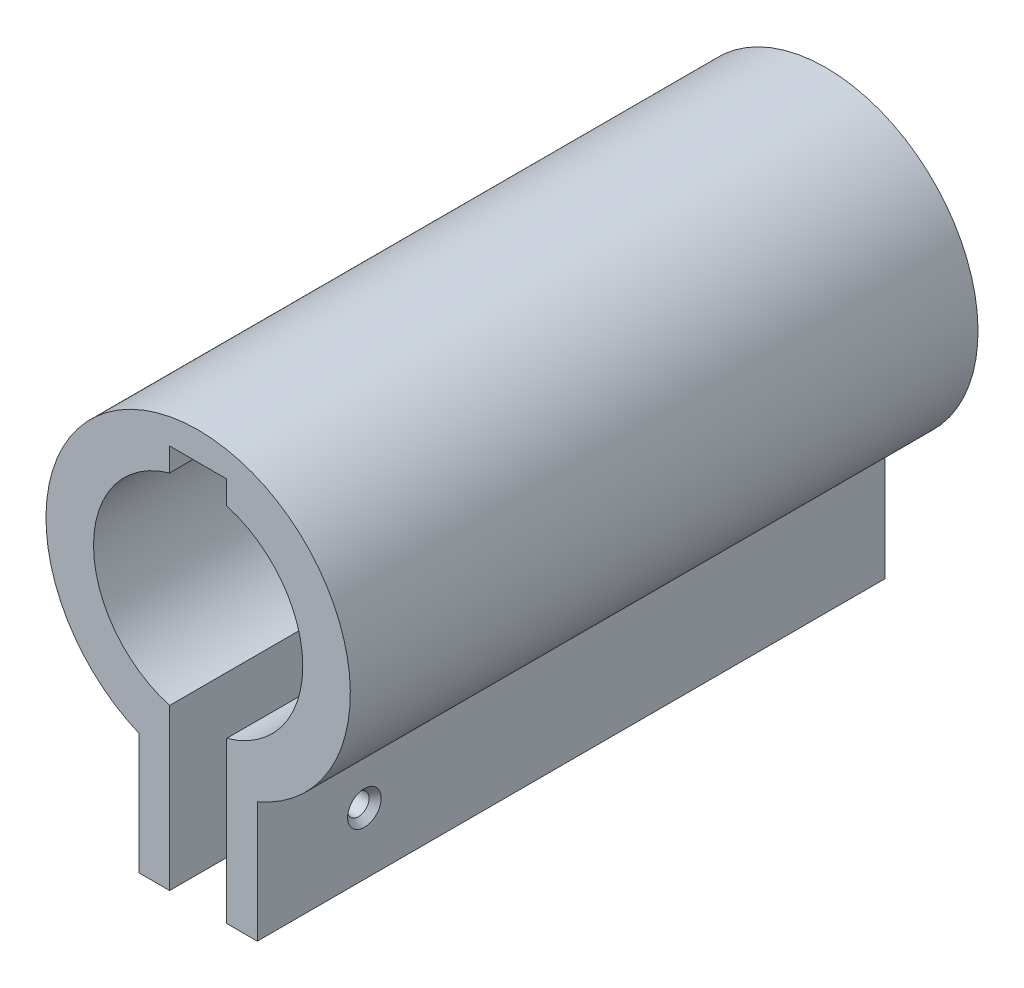
SolidWorks part; units mm, degrees
ref_plane "Front Plane" through (0, 0, 0) normal (0, 0, 1) x (1, 0, 0)
ref_plane "Top Plane" through (0, 0, 0) normal (0, 1, 0) x (1, 0, 0)
ref_plane "Right Plane" through (0, 0, 0) normal (1, 0, 0) x (0, 0, -1)
sketch "Sketch1" plane through (0, 0, 0) normal (0, 0, 1) x (1, 0, 0)
  circle A0 centre (0, 0) radius 11
  circle A1 centre (0, 0) radius 16
  dimension "D1" = 22
  dimension "D2" = 5
extrude "Boss-Extrude1" add sketch "Sketch1" along normal blind 33 and the other way blind 33
sketch "Sketch2" plane through (0, 0, 33) normal (0, 0, 1) x (1, 0, 0)
  line L0 (-3, 10.5402) -> (-3, 13.0402)
  line L2 (3, 13.0402) -> (3, 10.5402)
  line L3 (0, 0) -> (0, 13.0402) construction
  line L4 (-3, 13.0402) -> (0, 13.0402)
  line L5 (0, 13.0402) -> (3, 13.0402)
  line L6 (0, 0) -> (-3, 10.5402) construction
  line L7 (0, 0) -> (3, 10.5402) construction
  arc A0 (-3, 10.5402) -> (3, 10.5402) centre (0, 0) cw
  dimension "D1" = 3
  dimension "D2" = 3
  dimension "D3" = 2.5
extrude "Cut-Extrude1" cut sketch "Sketch2" against normal blind 33
mirror "Mirror2" about plane through (0, 0, 0) normal (0, 0, -1) of "Cut-Extrude1"
sketch "Sketch3" plane through (0, 0, 33) normal (0, 0, 1) x (1, 0, 0)
  line L0 (-3, -10.583) -> (-3, -15.7162)
  line L1 (-3, -15.7162) -> (-3, -10.583)
  line L2 (3, -10.583) -> (3, -15.7162)
  line L3 (-3, -10.583) -> (3, -10.583)
  line L4 (-3, -15.7162) -> (-3, -27.4422)
  line L5 (-3, -27.4422) -> (-6.2184, -27.4422)
  line L6 (-6.2184, -27.4422) -> (-6.2184, -14.7422)
  line L7 (-6.2184, -14.7422) -> (-3, -14.7422)
  line L8 (3, -15.7162) -> (3, -27.4422)
  line L9 (3, -27.4422) -> (6.2184, -27.4422)
  line L10 (6.2184, -27.4422) -> (6.2184, -14.7422)
  line L11 (6.2184, -14.7422) -> (3, -14.7422)
  arc A0 (-3, 10.583) -> (3, 10.583) centre (0, 0) ccw construction
  circle A1 centre (0, 0) radius 16 construction
  circle M6 centre (0, 0) radius 16
  dimension "D1" = 12.7
extrude "Boss-Extrude2" add sketch "Sketch3" against normal through all contours L6 L5 L4 M6 | L9 L10 L8 M6 region at (-4.6307, -21.3633, 33) region at (4.6307, -21.3633, 33)
sketch "Sketch4" plane through (0, 0, 33) normal (0, 0, 1) x (1, 0, 0)
  line L0 (-3, -10.583) -> (-3, -16.2715)
  line L1 (-3, -10.583) -> (3, -10.583)
  line L2 (3, -10.583) -> (3, -15.7162)
  line L3 (-3, -15.7162) -> (-3, -27.4422) construction
  line L4 (-3, -16.2715) -> (3, -16.2715)
  line L5 (3, -15.7162) -> (3, -27.4422) construction
  line L6 (3, -16.2715) -> (3, -15.7162)
  arc A0 (-3, 10.583) -> (3, 10.583) centre (0, 0) ccw construction
extrude "Cut-Extrude4" cut sketch "Sketch4" against normal through all
sketch "Sketch6" plane through (6.2184, 0, 0) normal (1, 0, 0) x (0, 0, -1)
  circle A0 centre (-21.7389, -20.9335) radius 1.42
  dimension "D1" = 2.84
hole_wizard "#4-40 Tapped Hole2" positions "Sketch7" profile "Sketch8" tap size "#4-40" standard "ANSI Inch" end condition through all
sketch "Sketch7" plane through (6.2184, 0, 0) normal (1, 0, 0) x (0, 0, -1)
  point P0 (-21.7389, -20.9335)
sketch "Sketch8" plane through (6.2184, -20.9335, 21.7389) normal (0, 1, 0) x (0, 0, -1)
  line L0 (0, 0) -> (0, 22.2184)
  line L1 (0, 22.2184) -> (1.1303, 22.2184)
  line L2 (1.1303, 22.2184) -> (1.1303, 0.635)
  line L3 (1.1303, 0.635) -> (1.7653, 0)
  line L5 (1.7653, 0) -> (0, 0)
  line L6 (-1.1303, 0.635) -> (-1.7653, 0) construction
  line L11 (0, -6.35) -> (0, 107.95) construction
  dimension "Thru Tap Drill Dia." = 2.2606
  dimension "Thru Tap Drill Depth" = 22.2184
  dimension "Near C'Sink Dia." = 3.5306
  dimension "Near C'Sink Angle" = 90
cosmetic thread "Hole Thread2" parameters "D2"=2.8448
